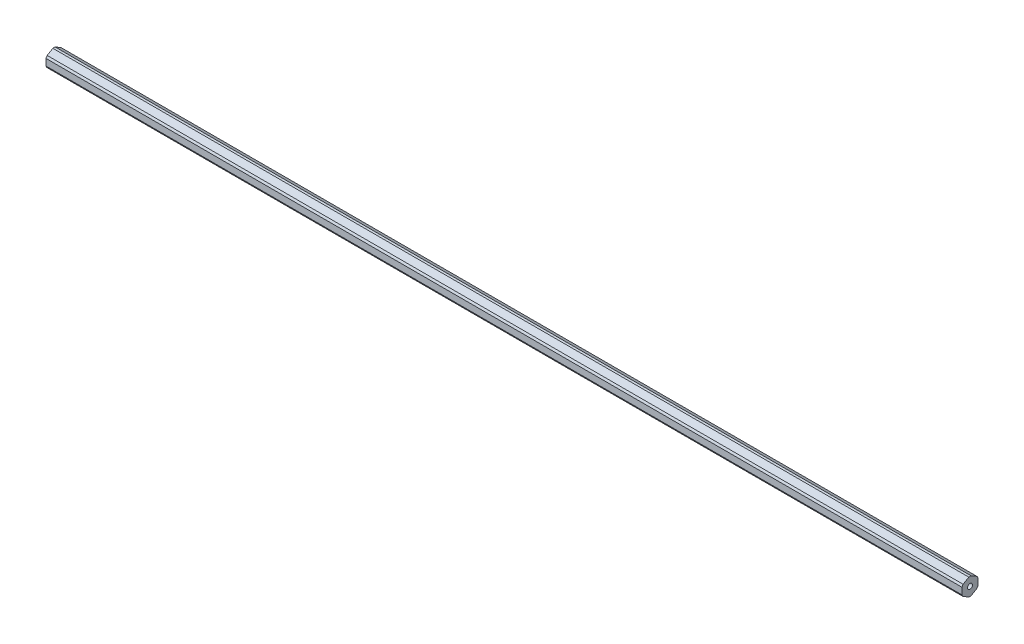
SolidWorks part; units mm, degrees
material "6061 Alloy"
ref_plane "Front Plane" through (0, 0, 0) normal (0, 0, 1) x (1, 0, 0)
ref_plane "Top Plane" through (0, 0, 0) normal (0, 1, 0) x (1, 0, 0)
ref_plane "Right Plane" through (0, 0, 0) normal (1, 0, 0) x (0, 0, -1)
ref_plane "Plane1" through (914.4, 0, 0) normal (1, 0, 0) x (0, 0, -1)
sketch "Sketch1" plane through (914.4, 0, 0) normal (1, 0, 0) x (0, 0, -1)
  line L0 (-5.4343, -4.1949) -> (-0.9157, -6.8037)
  line L1 (0.9157, -6.8037) -> (5.4343, -4.1949)
  line L2 (6.35, -2.6088) -> (6.35, 2.6088)
  line L3 (5.4343, 4.1949) -> (0.9157, 6.8037)
  line L4 (-0.9157, 6.8037) -> (-5.4343, 4.1949)
  line L5 (-6.35, 2.6088) -> (-6.35, -2.6088)
  circle A0 centre (0, 0) radius 1.9939
  arc A1 (-6.35, -2.6088) -> (-5.4343, -4.1949) centre (0, 0) ccw
  arc A2 (-0.9157, -6.8037) -> (0.9157, -6.8037) centre (0, 0) ccw
  arc A3 (5.4343, -4.1949) -> (6.35, -2.6088) centre (0, 0) ccw
  arc A4 (6.35, 2.6088) -> (5.4343, 4.1949) centre (0, 0) ccw
  arc A5 (0.9157, 6.8037) -> (-0.9157, 6.8037) centre (0, 0) ccw
  arc A6 (-5.4343, 4.1949) -> (-6.35, 2.6088) centre (0, 0) ccw
extrude "Boss-Extrude1" add sketch "Sketch1" against normal mid plane 723.9
equation "\"Hex Length\"= 28in + .5in"
equation "\"D1@Boss-Extrude1\"=\"Hex Length\""
